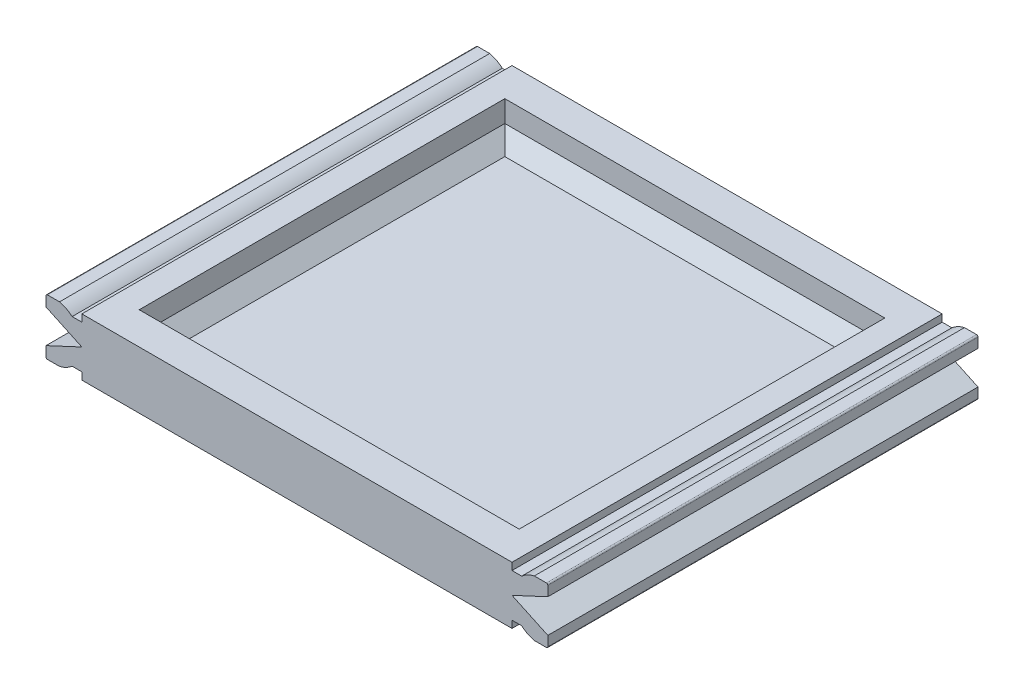
SolidWorks part; units mm, degrees
ref_plane "前视基准面" through (0, 0, 0) normal (0, 0, 1) x (1, 0, 0)
ref_plane "上视基准面" through (0, 0, 0) normal (0, 1, 0) x (1, 0, 0)
ref_plane "右视基准面" through (0, 0, 0) normal (1, 0, 0) x (0, 0, -1)
sketch "草图1" plane through (0, 0, 0) normal (0, 1, 0) x (1, 0, 0)
  line L0 (15, 15) -> (15, -15)
  line L1 (15, 15) -> (-15, 15)
  line L2 (15, -15) -> (-15, -15)
  line L3 (-15, 15) -> (-15, -15)
  line L4 (15, 15) -> (-15, -15) construction
  line L5 (15, -15) -> (-15, 15) construction
  point P1 (0, 0)
  dimension "D1" = 30
  dimension "D2" = 30
extrude "凸台-拉伸1" add sketch "草图1" along normal blind 2 and the other way blind 2
sketch "草图2" plane through (0, 2, 0) normal (0, 1, 0) x (1, 0, 0)
  line L0 (13.25, 12.75) -> (13.25, -12.75)
  line L1 (13.25, 12.75) -> (-13.25, 12.75)
  line L2 (13.25, -12.75) -> (-13.25, -12.75)
  line L3 (-13.25, 12.75) -> (-13.25, -12.75)
  line L4 (13.25, 12.75) -> (-13.25, -12.75) construction
  line L5 (13.25, -12.75) -> (-13.25, 12.75) construction
  point P1 (0, 0)
  dimension "D1" = 25.5
  dimension "D2" = 26.5
extrude "切除-拉伸1" cut sketch "草图2" against normal blind 2.5
chamfer "倒角1" distance 1 angle 45 4 edges at (13.25, -0.5, 0) (0, -0.5, 12.75) (-13.25, -0.5, 0) (0, -0.5, -12.75)
sketch "草图3" plane through (0, 0, 0) normal (0, 0, 1) x (1, 0, 0)
  line L0 (15, 0) -> (17, 0) construction
  line L1 (15, -2) -> (15, 2) construction
  line L2 (17, 0) -> (17.5, 0) construction
  line L3 (15, 1.5) -> (15, 0)
  line L4 (15, 1.5) -> (15.6771, 1.5)
  line L5 (17.5, 1.1658) -> (17.5, 1.95)
  line L6 (17.5, 1.95) -> (16.5556, 1.95)
  line L7 (15, 0) -> (17.5, 1.1658)
  arc A0 (16.5556, 1.95) -> (15.6771, 1.5) centre (17, 0) ccw
  dimension "D5" = 2
  dimension "D1" = 2
  dimension "D2" = 0.5
  dimension "D3" = 1.5
  dimension "D4" = 1.95
  dimension "D6" = 25
  dimension "D7" = 1.1658
extrude "凸台-拉伸2" add sketch "草图3" along normal blind 15 and the other way blind 15 contours L6 A0 L4 L7 L5 region at (16.1553, 1.1423, 0)
mirror "镜向1" about plane through (0, 0, 0) normal (0, 1, 0) of "凸台-拉伸2"
mirror "镜向2" about plane through (0, 0, 0) normal (1, 0, 0) of "镜向1", "凸台-拉伸2"
fillet "圆角1" radius 0.1 4 edges at (17.5, -1.95, 0) (17.5, 1.95, 0) (-17.5, -1.95, 0) (-17.5, 1.95, 0)
